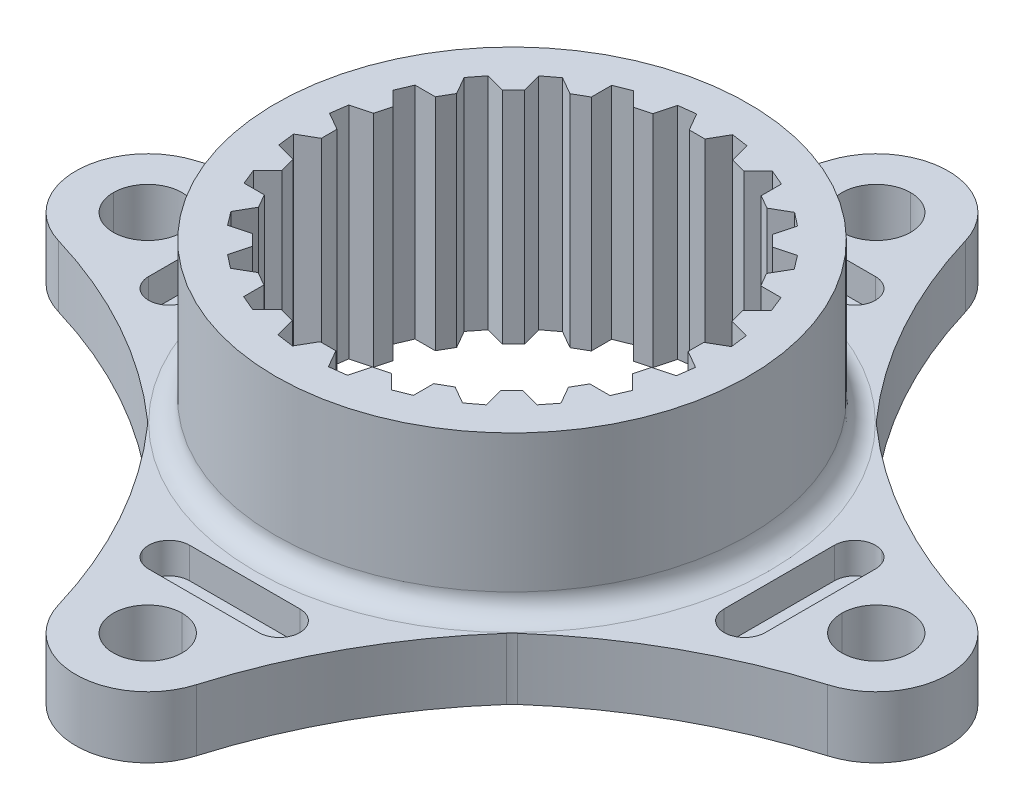
SolidWorks part; units mm, degrees
ref_plane "Front Plane" through (0, 0, 0) normal (0, 0, 1) x (1, 0, 0)
ref_plane "Top Plane" through (0, 0, 0) normal (0, 1, 0) x (1, 0, 0)
ref_plane "Right Plane" through (0, 0, 0) normal (1, 0, 0) x (0, 0, -1)
sketch "Sketch1" plane through (0, 0, 0) normal (0, 1, 0) x (1, 0, 0)
  line L0 (274.6284, 454.6081) -> (780.6456, 454.6081) construction
  circle A0 centre (0, 0) radius 23
  dimension "D1" = 46
sketch "Sketch5" plane through (0, 0, 0) normal (0, 1, 0) x (1, 0, 0)
  circle A0 centre (0, 0) radius 23
  circle A1 centre (0, 0) radius 25
  dimension "D1" = 46
  dimension "D2" = 50
sketch "Sketch6" plane through (0, 0, 0) normal (0, 1, 0) x (1, 0, 0)
  line L0 (-0.9689, -22.7363) -> (0.9689, -22.7363)
  line L1 (0.9689, -22.7363) -> (2.2189, -24.9013)
  line L2 (0, 33.3652) -> (0, -36.4848) construction
  line L3 (-0.9689, -22.7363) -> (-2.2189, -24.9013)
  line L4 (-4.9456, -22.1943) -> (-4.2985, -24.6091)
  line L5 (-6.8174, -21.6927) -> (-4.9456, -22.1943)
  line L6 (-6.8174, -21.6927) -> (-8.5852, -23.4605)
  line L7 (-10.5182, -22.6399) -> (-8.5852, -23.4605)
  line L8 (-10.5182, -20.1399) -> (-10.5182, -22.6399)
  line L9 (-12.1965, -19.171) -> (-10.5182, -20.1399)
  line L10 (-12.1965, -19.171) -> (-14.3615, -20.421)
  line L11 (-16.0164, -19.1281) -> (-14.3615, -20.421)
  line L12 (-15.3693, -16.7133) -> (-16.0164, -19.1281)
  line L13 (-16.7396, -15.343) -> (-15.3693, -16.7133)
  line L14 (-16.7396, -15.343) -> (-19.1544, -15.99)
  line L15 (-20.4182, -14.3129) -> (-19.1544, -15.99)
  line L16 (-19.1682, -12.1478) -> (-20.4182, -14.3129)
  line L17 (-20.1372, -10.4696) -> (-19.1682, -12.1478)
  line L18 (-20.1372, -10.4696) -> (-22.6372, -10.4696)
  line L19 (-23.4239, -8.5225) -> (-22.6372, -10.4696)
  line L20 (-21.6561, -6.7547) -> (-23.4239, -8.5225)
  line L21 (-22.1576, -4.8829) -> (-21.6561, -6.7547)
  line L22 (-22.1576, -4.8829) -> (-24.5725, -4.2358)
  line L23 (-24.8284, -2.1515) -> (-24.5725, -4.2358)
  line L24 (-22.6633, -0.9015) -> (-24.8284, -2.1515)
  line L25 (-22.6633, 1.0364) -> (-22.6633, -0.9015)
  line L26 (-22.6633, 1.0364) -> (-24.8284, 2.2864)
  line L27 (-24.5361, 4.366) -> (-24.8284, 2.2864)
  line L28 (-22.1213, 5.013) -> (-24.5361, 4.366)
  line L29 (-21.6197, 6.8849) -> (-22.1213, 5.013)
  line L30 (-21.6197, 6.8849) -> (-23.3875, 8.6526)
  line L31 (-22.567, 10.5857) -> (-23.3875, 8.6526)
  line L32 (-20.067, 10.5857) -> (-22.567, 10.5857)
  line L33 (-19.098, 12.2639) -> (-20.067, 10.5857)
  line L34 (-19.098, 12.2639) -> (-20.348, 14.429)
  line L35 (-19.0552, 16.0838) -> (-20.348, 14.429)
  line L36 (-16.6403, 15.4368) -> (-19.0552, 16.0838)
  line L37 (-15.27, 16.8071) -> (-16.6403, 15.4368)
  line L38 (-15.27, 16.8071) -> (-15.9171, 19.2219)
  line L39 (-14.24, 20.4857) -> (-15.9171, 19.2219)
  line L40 (-12.0749, 19.2357) -> (-14.24, 20.4857)
  line L41 (-10.3966, 20.2046) -> (-12.0749, 19.2357)
  line L42 (-10.3966, 20.2046) -> (-10.3966, 22.7046)
  line L43 (-8.4496, 23.4913) -> (-10.3966, 22.7046)
  line L44 (-6.6818, 21.7235) -> (-8.4496, 23.4913)
  line L45 (-4.8099, 22.2251) -> (-6.6818, 21.7235)
  line L46 (-4.8099, 22.2251) -> (-4.1629, 24.6399)
  line L47 (-2.0785, 24.8958) -> (-4.1629, 24.6399)
  line L48 (-0.8285, 22.7308) -> (-2.0785, 24.8958)
  line L49 (1.1093, 22.7308) -> (-0.8285, 22.7308)
  line L50 (1.1093, 22.7308) -> (2.3593, 24.8958)
  line L51 (4.4389, 24.6036) -> (2.3593, 24.8958)
  line L52 (5.086, 22.1888) -> (4.4389, 24.6036)
  line L53 (6.9578, 21.6872) -> (5.086, 22.1888)
  line L54 (6.9578, 21.6872) -> (8.7256, 23.455)
  line L55 (10.6586, 22.6344) -> (8.7256, 23.455)
  line L56 (10.6586, 20.1344) -> (10.6586, 22.6344)
  line L57 (12.3369, 19.1655) -> (10.6586, 20.1344)
  line L58 (12.3369, 19.1655) -> (14.5019, 20.4155)
  line L59 (16.1568, 19.1226) -> (14.5019, 20.4155)
  line L60 (15.5097, 16.7078) -> (16.1568, 19.1226)
  line L61 (16.88, 15.3375) -> (15.5097, 16.7078)
  line L62 (16.88, 15.3375) -> (19.2948, 15.9845)
  line L63 (20.5586, 14.3074) -> (19.2948, 15.9845)
  line L64 (19.3086, 12.1424) -> (20.5586, 14.3074)
  line L65 (20.2776, 10.4641) -> (19.3086, 12.1424)
  line L66 (20.2776, 10.4641) -> (22.7776, 10.4641)
  line L67 (23.5643, 8.517) -> (22.7776, 10.4641)
  line L68 (21.7965, 6.7492) -> (23.5643, 8.517)
  line L69 (22.298, 4.8774) -> (21.7965, 6.7492)
  line L70 (22.298, 4.8774) -> (24.7129, 4.2303)
  line L71 (24.9688, 2.146) -> (24.7129, 4.2303)
  line L72 (22.8037, 0.896) -> (24.9688, 2.146)
  line L73 (22.8037, -1.0419) -> (22.8037, 0.896)
  line L74 (22.8037, -1.0419) -> (24.9688, -2.2919)
  line L75 (24.6765, -4.3714) -> (24.9688, -2.2919)
  line L76 (22.2617, -5.0185) -> (24.6765, -4.3714)
  line L77 (21.7601, -6.8903) -> (22.2617, -5.0185)
  line L78 (21.7601, -6.8903) -> (23.5279, -8.6581)
  line L79 (22.7074, -10.5912) -> (23.5279, -8.6581)
  line L80 (20.2074, -10.5912) -> (22.7074, -10.5912)
  line L81 (19.2384, -12.2694) -> (20.2074, -10.5912)
  line L82 (19.2384, -12.2694) -> (20.4884, -14.4345)
  line L83 (19.1955, -16.0893) -> (20.4884, -14.4345)
  line L84 (16.7807, -15.4423) -> (19.1955, -16.0893)
  line L85 (15.4104, -16.8126) -> (16.7807, -15.4423)
  line L86 (15.4104, -16.8126) -> (16.0575, -19.2274)
  line L87 (14.3804, -20.4912) -> (16.0575, -19.2274)
  line L88 (12.2153, -19.2412) -> (14.3804, -20.4912)
  line L89 (10.537, -20.2101) -> (12.2153, -19.2412)
  line L90 (10.537, -20.2101) -> (10.537, -22.7101)
  line L91 (8.59, -23.4968) -> (10.537, -22.7101)
  line L92 (6.8222, -21.729) -> (8.59, -23.4968)
  line L93 (4.9503, -22.2306) -> (6.8222, -21.729)
  line L94 (4.9503, -22.2306) -> (4.3033, -24.6454)
  line L95 (2.2189, -24.9013) -> (4.3033, -24.6454)
  line L96 (-4.2985, -24.6091) -> (-2.2189, -24.9013)
  circle A0 centre (0, 0) radius 23 construction
  circle A1 centre (0, 0) radius 25 construction
  point P11 (0, -23)
  point P131 (0.0702, -0.0027)
  dimension "D4" = 2.5
  dimension "D1" = 2.1
  dimension "D5" = 112
  dimension "D6" = 120
  dimension "D2" = 1.9379
  dimension "D3" = 24
sketch "Sketch8" plane through (0, 0, 0) normal (0, 1, 0) x (1, 0, 0)
  circle A0 centre (0, 0) radius 100
  circle A1 centre (0, 0) radius 28.956
  point P3 (0, -1.1769)
  dimension "D1" = 200
extrude "Boss-Extrude4" add sketch "Sketch8" along normal blind 27.178 contours A0
extrude "Cut-Extrude1" cut sketch "Sketch6" along normal through all
sketch "Sketch9" plane through (0, 27.178, 0) normal (0, 1, 0) x (1, 0, 0)
  circle A0 centre (0, 0) radius 29.21
  dimension "D1" = 58.42
extrude "Cut-Extrude3" cut sketch "Sketch9" against normal blind 19.558 flip side to cut
sketch "Sketch10" plane through (0, 7.62, 0) normal (0, 1, 0) x (1, 0, 0)
  circle A1 centre (0, 45.0088) radius 4.2545
  circle A4 centre (45.0088, 0) radius 4.2545
  circle A5 centre (0, -45.0088) radius 4.2545
  circle A6 centre (-45.0088, 0) radius 4.2545
  point P11 (0, 0)
  point P28 (0, 0)
  dimension "D1" = 4
  dimension "D2" = 8.509
  dimension "D3" = 45.0088
sketch "Sketch11" plane through (0, 7.62, 0) normal (0, 1, 0) x (1, 0, 0)
  line L0 (0, 45.0088) -> (45.0088, 0) construction
  line L1 (0, 0) -> (70.7107, 70.7107) construction
  line L2 (0, 45.0088) -> (8.89, 45.0088) construction
  line L3 (0, 45.0088) -> (8.5239, 47.5337) construction
  circle A0 centre (0, 0) radius 100 construction
  arc A1 (8.5239, 47.5337) -> (22.5044, 22.5044) centre (71.1084, 66.0721) ccw
  arc A2 (47.5337, 8.5239) -> (22.5044, 22.5044) centre (66.0721, 71.1084) cw
  arc A3 (47.5337, -8.5239) -> (22.5044, -22.5044) centre (66.0721, -71.1084) ccw
  arc A4 (-8.5239, -47.5337) -> (-22.5044, -22.5044) centre (-71.1084, -66.0721) ccw
  arc A5 (-47.5337, 8.5239) -> (-22.5044, 22.5044) centre (-66.0721, 71.1084) ccw
  arc A6 (8.5239, -47.5337) -> (22.5044, -22.5044) centre (71.1084, -66.0721) cw
  arc A7 (-47.5337, -8.5239) -> (-22.5044, -22.5044) centre (-66.0721, -71.1084) cw
  circle A8 centre (0, 45.0088) radius 8.89
  circle A9 centre (45.0088, 0) radius 8.89
  circle A10 centre (0, -45.0088) radius 8.89
  circle A11 centre (-45.0088, 0) radius 8.89
  arc A12 (-8.5239, 47.5337) -> (-22.5044, 22.5044) centre (-71.1084, 66.0721) cw
  point P15 (0, 0)
  point P31 (0, 0)
  point P37 (0, 0)
  point P42 (0, 0)
  point P51 (0, 0)
  circle M10 centre (0, 0) radius 100
  dimension "D4" = 4
  dimension "D1" = 4
  dimension "D2" = 17.78
  dimension "D5" = 4
  dimension "D3" = 16.5
extrude "Cut-Extrude6" cut sketch "Sketch11" against normal blind 7.62 contours A11 A8 A9 A10 M10 region at (-97.1716, 7.62, 0)
extrude "Cut-Extrude7" cut sketch "Sketch10" against normal blind 7.62
fillet "Fillet2" radius 2.54 1 edges at (0, 7.62, 29.21)
ref_plane "Plane1" through (0, 0, 0) normal (0, 0, 1) x (1, 0, 0)
ref_plane "Plane2" through (0, 0, 0) normal (-1, 0, 0) x (0, 0, 1)
split line "Split Line1"
split line "Split Line2"
ref_axis "Axis1" through (0, 8.001, 0) along (0, -1, 0)
fillet "Fillet3" radius 7.62 4 edges at (-22.5044, 3.81, -22.5044) (22.5044, 3.81, -22.5044) (22.5044, 3.81, 22.5044) (-22.5044, 3.81, 22.5044)
sketch "Sketch13" plane through (0, 7.62, 0) normal (0, 1, 0) x (1, 0, 0)
  line L0 (0, 4.191) -> (0, -4.191) construction
  line L1 (-8.4262, 38.1) -> (8.4262, 38.1)
  line L2 (-8.4262, 38.1) -> (-10.795, 33.02)
  line L3 (-10.795, 33.02) -> (10.795, 33.02)
  line L4 (8.4262, 38.1) -> (10.795, 33.02)
  point P4 (-11.7544, 32.9848)
  point P5 (0, 0)
  point P6 (0, 0)
  point P7 (8.4622, 33.218)
  point P8 (11.3769, 32.9848)
  point P11 (0, 33.02)
  dimension "D1" = 115
  dimension "D2" = 115
  dimension "D3" = 5.08
  dimension "D4" = 0
  dimension "D5" = 21.59
  dimension "D6" = 33.02
extrude "Cut-Extrude12" cut sketch "Sketch13" against normal blind 3.81 contours L1 L4 L3 L2
fillet "Fillet5" radius 2.54 4 edges at (-10.795, 5.715, -33.02) (10.795, 5.715, -33.02) (-8.4262, 5.715, -38.1) (8.4262, 5.715, -38.1)
pattern_circular "CirPattern1" count 4 over 360 about axis through (0, 8.001, 0) along (0, -1, 0) of "Cut-Extrude12", "Fillet5"
